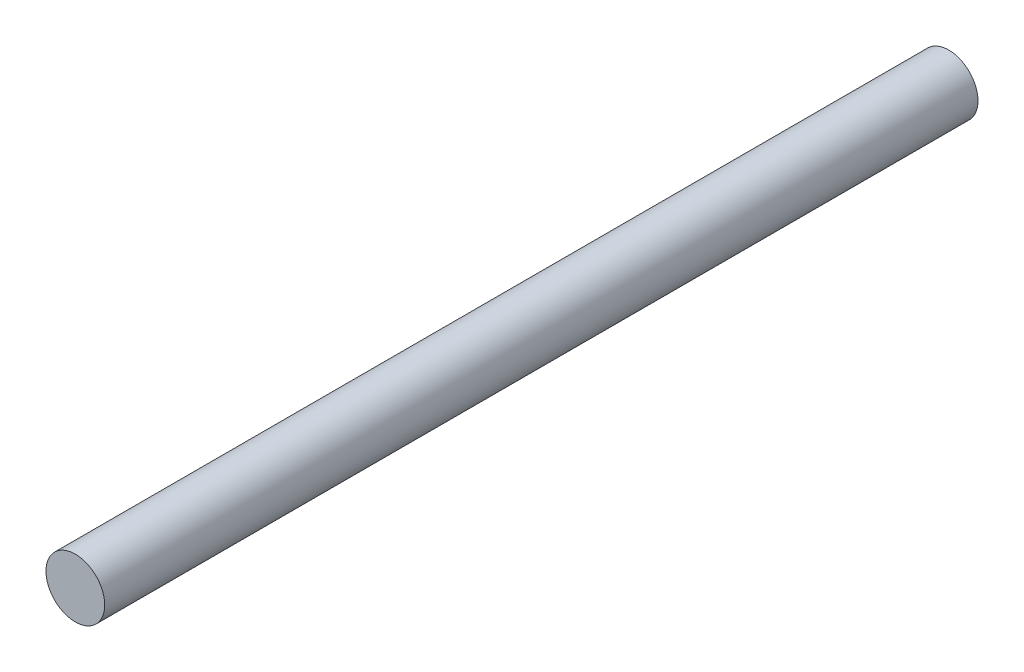
SolidWorks part; units mm, degrees
ref_plane "Front Plane" through (0, 0, 0) normal (0, 0, 1) x (1, 0, 0)
ref_plane "Top Plane" through (0, 0, 0) normal (0, 1, 0) x (1, 0, 0)
ref_plane "Right Plane" through (0, 0, 0) normal (1, 0, 0) x (0, 0, -1)
sketch "Sketch1" plane through (0, 0, 0) normal (0, 0, 1) x (1, 0, 0)
  circle A0 centre (0, 0) radius 2.49
  dimension "D1" = 4.98
extrude "Boss-Extrude1" add sketch "Sketch1" along normal blind 10 and the other way blind 64
sketch "Sketch2" plane through (0, 0, 0) normal (0, 0, 1) x (1, 0, 0)
  circle A0 centre (0, 0) radius 2.5 construction
  dimension "D1" = 5
